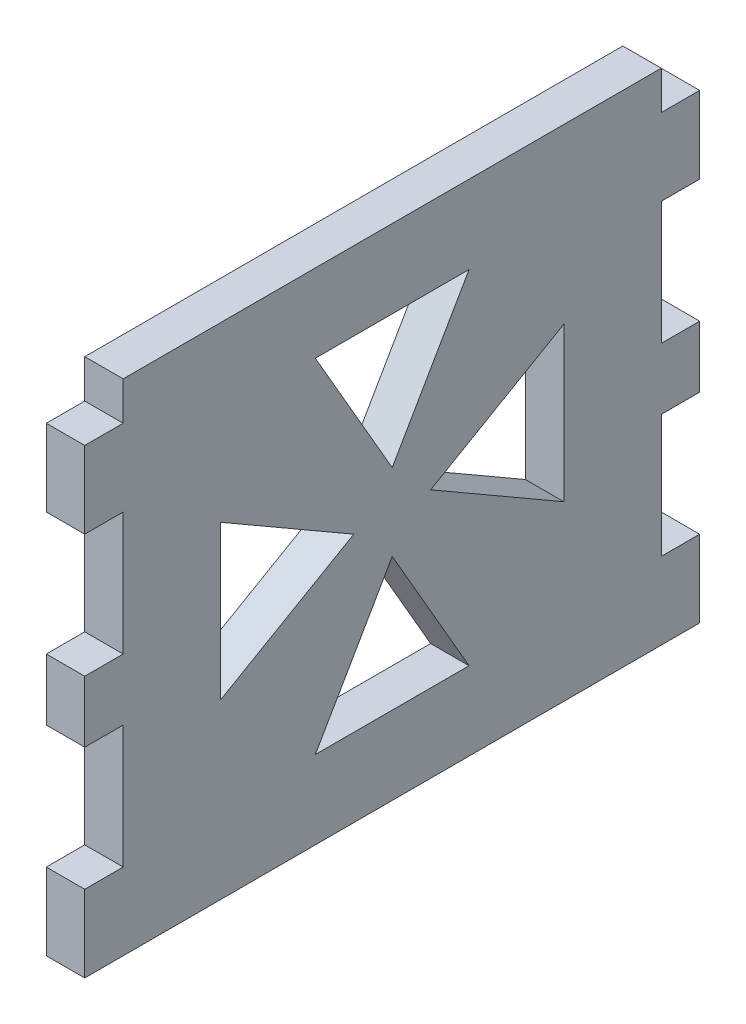
SolidWorks part; units mm, degrees
material "Pine"
ref_plane "Front Plane" through (0, 0, 0) normal (0, 0, 1) x (1, 0, 0)
ref_plane "Top Plane" through (0, 0, 0) normal (0, 1, 0) x (1, 0, 0)
ref_plane "Right Plane" through (0, 0, 0) normal (1, 0, 0) x (0, 0, -1)
sketch "Sketch1" plane through (0, 0, 0) normal (1, 0, 0) x (0, 0, -1)
  line L0 (50.8, 0) -> (50.8, 88.9) construction
  line L1 (0, 0) -> (101.6, 0)
  line L2 (0, 0) -> (0, 88.9)
  line L3 (0, 88.9) -> (101.6, 88.9)
  line L4 (101.6, 0) -> (101.6, 88.9)
  line L5 (0, 0) -> (6.35, 0)
  line L6 (0, 0) -> (0, 6.35)
  line L7 (0, 6.35) -> (6.35, 6.35)
  line L8 (6.35, 0) -> (6.35, 6.35)
  line L9 (101.6, 0) -> (95.25, 0)
  line L10 (101.6, 0) -> (101.6, 6.35)
  line L11 (101.6, 6.35) -> (95.25, 6.35)
  line L12 (95.25, 0) -> (95.25, 6.35)
  line L13 (0, 88.9) -> (6.35, 88.9)
  line L14 (0, 88.9) -> (0, 82.55)
  line L15 (0, 82.55) -> (6.35, 82.55)
  line L16 (6.35, 88.9) -> (6.35, 82.55)
  line L17 (101.6, 88.9) -> (95.25, 88.9)
  line L18 (101.6, 88.9) -> (101.6, 82.55)
  line L19 (101.6, 82.55) -> (95.25, 82.55)
  line L20 (95.25, 88.9) -> (95.25, 82.55)
  line L21 (101.6, 69.85) -> (95.25, 69.85)
  line L22 (101.6, 69.85) -> (101.6, 49.53)
  line L23 (101.6, 49.53) -> (95.25, 49.53)
  line L24 (95.25, 69.85) -> (95.25, 49.53)
  line L25 (101.6, 19.05) -> (95.25, 19.05)
  line L26 (101.6, 19.05) -> (101.6, 39.37)
  line L27 (101.6, 39.37) -> (95.25, 39.37)
  line L28 (95.25, 19.05) -> (95.25, 39.37)
  line L29 (0, 39.37) -> (6.35, 39.37)
  line L30 (6.35, 19.05) -> (6.35, 39.37)
  line L31 (0, 19.05) -> (6.35, 19.05)
  line L32 (0, 19.05) -> (0, 39.37)
  line L33 (0, 49.53) -> (6.35, 49.53)
  line L34 (6.35, 69.85) -> (6.35, 49.53)
  line L35 (0, 69.85) -> (6.35, 69.85)
  line L36 (0, 69.85) -> (0, 49.53)
  line L37 (6.35, 6.35) -> (95.25, 6.35)
  point P25 (98.425, 69.85)
  dimension "D1" = 101.6
  dimension "D2" = 88.9
  dimension "D3" = 6.35
  dimension "D4" = 6.35
  dimension "D5" = 6.35
  dimension "D6" = 6.35
  dimension "D7" = 6.35
  dimension "D8" = 6.35
  dimension "D9" = 6.35
  dimension "D10" = 6.35
  dimension "D11" = 12.7
  dimension "D12" = 12.7
  dimension "D13" = 20.32
  dimension "D14" = 20.32
extrude "Boss-Extrude1" add sketch "Sketch1" along normal blind 6.35 contours L1 L0 L3 L16 L15 L2 L35 L34 L33 L29 L30 L31 L7 L8 | L0 L1 L12 L11 L4 L25 L28 L27 L23 L24 L21 L19 L20 L3 region at (0, 47.4409, -50.8)
sketch "Sketch2" plane through (6.35, 0, 0) normal (1, 0, 0) x (0, 0, -1)
  line L0 (50.8, 88.9) -> (50.8, 6.35) construction
  line L1 (44.45, 47.625) -> (22.453, 60.325)
  line L2 (22.453, 60.325) -> (22.453, 34.925)
  line L3 (22.453, 34.925) -> (44.45, 47.625)
  line L4 (6.35, 88.9) -> (95.25, 88.9) construction
  line L5 (0, 6.35) -> (101.6, 6.35) construction
  line L6 (50.8, 53.975) -> (63.5, 75.972)
  line L7 (101.6, 39.37) -> (101.6, 49.53) construction
  line L8 (101.6, 47.625) -> (0, 47.625) construction
  line L9 (0, 39.37) -> (0, 49.53) construction
  line L10 (63.5, 75.972) -> (38.1, 75.972)
  line L11 (38.1, 75.972) -> (50.8, 53.975)
  line L12 (57.15, 47.625) -> (79.147, 34.925)
  line L13 (79.147, 34.925) -> (79.147, 60.325)
  line L14 (79.147, 60.325) -> (57.15, 47.625)
  line L15 (50.8, 41.275) -> (38.1, 19.278)
  line L16 (38.1, 19.278) -> (63.5, 19.278)
  line L17 (63.5, 19.278) -> (50.8, 41.275)
  circle A0 centre (29.7853, 47.625) radius 7.3323 construction
  point P15 (29.7853, 47.625)
  point P19 (44.45, 47.625)
  point P20 (50.8, 47.625)
  point P29 (50.8, 47.625)
  dimension "D1" = 6.35
  dimension "=" = 41.275
  dimension "D2" = 4
  dimension "D3" = 25.4
extrude "Cut-Extrude1" cut sketch "Sketch2" against normal up to surface (6.35 mm away) up to face at (0, 51.3292, -50.8)
